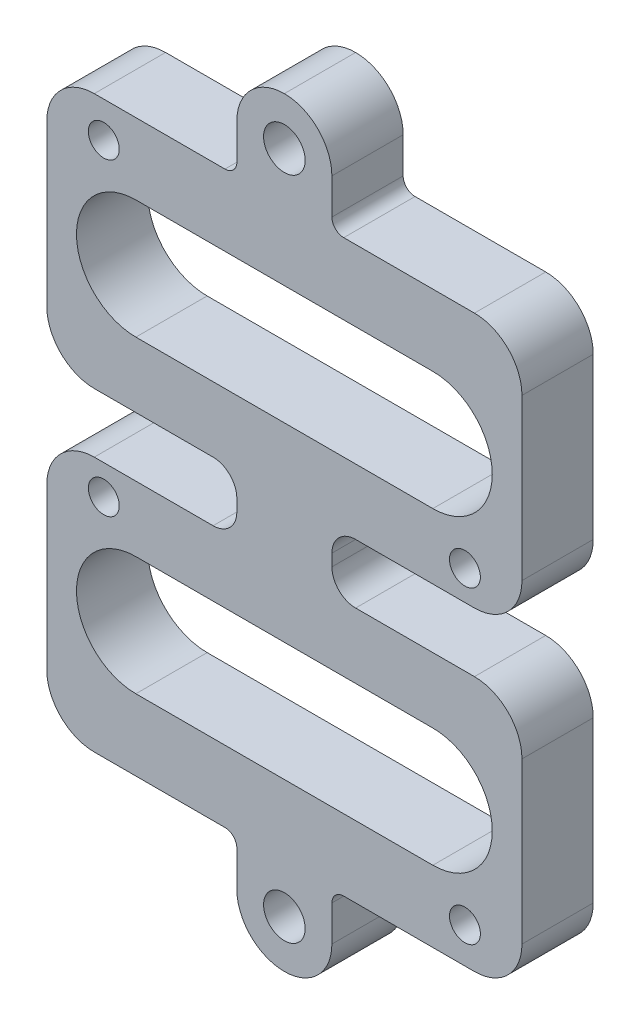
SolidWorks part; units mm, degrees
ref_plane "Top Plane" through (0, 0, 0) normal (0, 0, 1) x (1, 0, 0)
ref_plane "Right Plane" through (0, 0, 0) normal (0, 1, 0) x (1, 0, 0)
ref_plane "Front Plane" through (0, 0, 0) normal (1, 0, 0) x (0, 0, -1)
sketch "Sketch1" plane through (0, 0, 0) normal (0, 0, 1) x (1, 0, 0)
  line L0 (-20, 32) -> (20, -32) construction
  line L1 (-20, 32) -> (20, 32)
  line L2 (-20, 32) -> (-20, -32)
  line L3 (-20, -32) -> (20, -32)
  line L4 (20, 32) -> (20, -32)
  dimension "D1" = 40
  dimension "D2" = 64
extrude "Boss-Extrude1" add sketch "Sketch1" along normal mid plane 6
sketch "Sketch3" plane through (0, 0, 3) normal (0, 0, 1) x (1, 0, 0)
  line L0 (-15.2, 13) -> (15.2, 13) construction
  line L1 (-15.2, 21) -> (15.2, 21) construction
  line L2 (-15.2, 21) -> (-15.2, 5) construction
  line L3 (-15.2, 5) -> (15.2, 5) construction
  line L4 (15.2, 21) -> (15.2, 5) construction
  line L5 (0, 21) -> (0, 5) construction
  line L6 (-30.0979, 0) -> (31.9653, 0) construction
  line L7 (0, -21) -> (0, -5) construction
  line L8 (15.2, -21) -> (15.2, -5) construction
  line L9 (-15.2, -5) -> (15.2, -5) construction
  line L10 (-15.2, -21) -> (-15.2, -5) construction
  line L11 (-15.2, -21) -> (15.2, -21) construction
  line L12 (-15.2, -13) -> (15.2, -13) construction
  circle A0 centre (-15.2, 21) radius 1.3
  circle A1 centre (15.2, 21) radius 1.3 construction
  circle A2 centre (15.2, 5) radius 1.3
  circle A3 centre (-15.2, 5) radius 1.3 construction
  circle A4 centre (-15.2, -5) radius 1.3
  circle A5 centre (15.2, -5) radius 1.3 construction
  circle A6 centre (15.2, -21) radius 1.3
  circle A7 centre (-15.2, -21) radius 1.3 construction
  dimension "D3" = 2.6
  dimension "D1" = 16
  dimension "D2" = 30.4
  dimension "D4" = 10
extrude "Cut-Extrude2" cut sketch "Sketch3" against normal through all
sketch "Sketch4" plane through (0, 0, 3) normal (0, 0, 1) x (1, 0, 0)
  line L0 (-27.5916, 0) -> (32.0836, 0) construction
  circle A0 centre (0, -28) radius 1.75
  circle A1 centre (0, -28) radius 3 construction
  circle A2 centre (0, 28) radius 3 construction
  circle A3 centre (0, 28) radius 1.75
  point P9 (0, 0)
  dimension "D1" = 3.5
  dimension "D2" = 6
  dimension "D3" = 56
extrude "Cut-Extrude3" cut sketch "Sketch4" against normal through all
sketch "Sketch5" plane through (0, 0, 3) normal (0, 0, 1) x (1, 0, 0)
  line L0 (-20, 32) -> (-20, -32) construction
  line L1 (-20, -2.5) -> (-4, -2.5)
  line L2 (-20, -2.5) -> (-20, 2.5)
  line L3 (-20, 2.5) -> (-4, 2.5)
  line L4 (-4, -2.5) -> (-4, 2.5)
  line L5 (-23.6006, 0) -> (25.8311, 0) construction
  line L6 (0, -32) -> (0, 32) construction
  line L7 (-20, -32) -> (20, -32) construction
  line L8 (20, 32) -> (-20, 32) construction
  line L9 (4, -2.5) -> (4, 2.5)
  line L10 (20, 2.5) -> (4, 2.5)
  line L11 (20, -2.5) -> (20, 2.5)
  line L12 (20, -2.5) -> (4, -2.5)
  line L13 (4, -32) -> (4, -24)
  line L14 (-20, -32) -> (-4, -32)
  line L15 (-20, -32) -> (-20, -24)
  line L16 (-20, -24) -> (-4, -24)
  line L17 (-4, -32) -> (-4, -24)
  line L18 (20, -24) -> (4, -24)
  line L19 (20, -32) -> (20, -24)
  line L20 (20, -32) -> (4, -32)
  line L21 (20, 32) -> (4, 32)
  line L22 (20, 32) -> (20, 24)
  line L23 (20, 24) -> (4, 24)
  line L24 (-4, 32) -> (-4, 24)
  line L25 (-20, 24) -> (-4, 24)
  line L26 (-20, 32) -> (-20, 24)
  line L27 (-20, 32) -> (-4, 32)
  line L28 (4, 32) -> (4, 24)
  line L29 (12.5, -13) -> (-12.5, -13) construction
  line L30 (12.5, -18) -> (-12.5, -18)
  line L31 (12.5, -8) -> (-12.5, -8)
  line L32 (15.2, -21) -> (-15.2, -5) construction
  line L33 (12.5, 13) -> (-12.5, 13) construction
  line L34 (12.5, 18) -> (-12.5, 18)
  line L35 (12.5, 8) -> (-12.5, 8)
  arc A0 (12.5, -18) -> (12.5, -8) centre (12.5, -13) ccw
  arc A1 (-12.5, -8) -> (-12.5, -18) centre (-12.5, -13) ccw
  arc A2 (12.5, 18) -> (12.5, 8) centre (12.5, 13) cw
  arc A3 (-12.5, 8) -> (-12.5, 18) centre (-12.5, 13) cw
  point P9 (4, 0)
  point P10 (-4, 0)
  point P40 (0, -13)
  point P49 (0, 0)
  point P52 (0, 13)
  dimension "D6" = 5
  dimension "D1" = 5
  dimension "D2" = 8
  dimension "D3" = 8
  dimension "D4" = 8
  dimension "D5" = 25
extrude "Cut-Extrude4" cut sketch "Sketch5" against normal through all
fillet "Fillet1" radius 2 4 edges at (4, 2.5, 0) (4, -2.5, 0) (-4, 2.5, 0) (-4, -2.5, 0)
fillet "Fillet2" radius 4 12 edges at (4, -32, 0) (-4, -32, 0) (-4, 32, 0) (4, 32, 0) (20, 24, 0) (20, 2.5, 0) (-20, 24, 0) (-20, 2.5, 0) (-20, -24, 0) (-20, -2.5, 0) (20, -24, 0) (20, -2.5, 0)
fillet "Fillet3" radius 1 4 edges at (4, 24, 0) (-4, 24, 0) (-4, -24, 0) (4, -24, 0)
